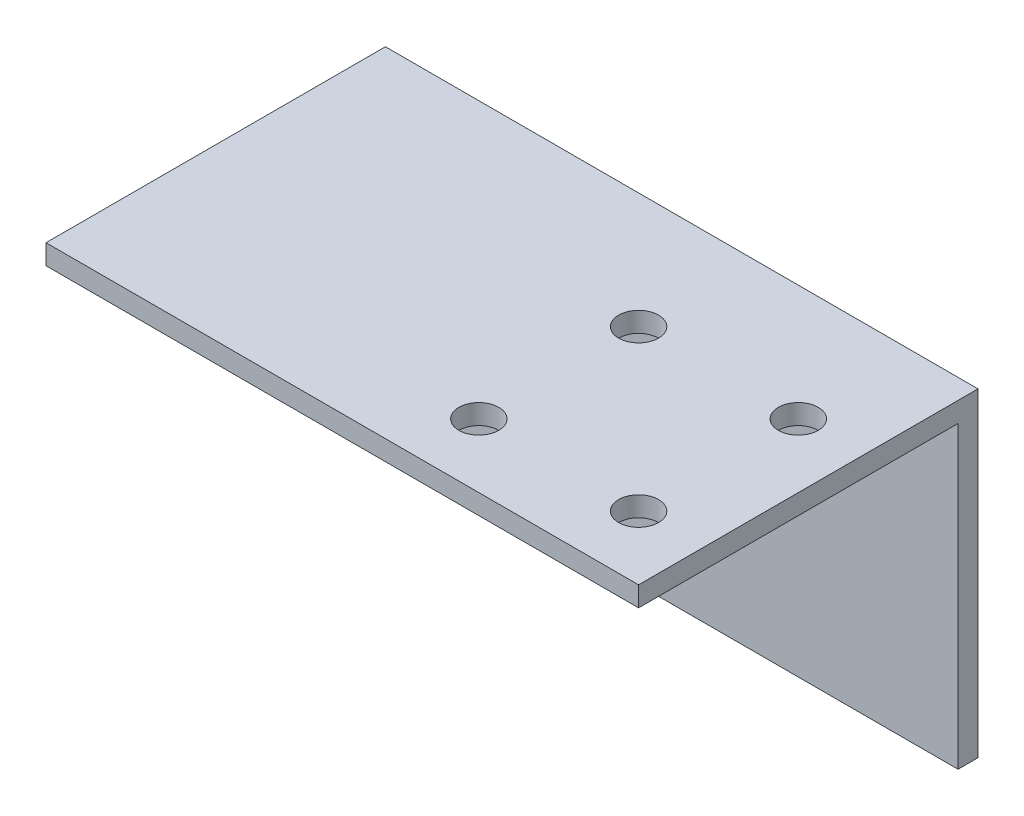
SolidWorks part; units mm, degrees
ref_plane "Front Plane" through (0, 0, 0) normal (0, 0, 1) x (1, 0, 0)
ref_plane "Top Plane" through (0, 0, 0) normal (0, 1, 0) x (1, 0, 0)
ref_plane "Right Plane" through (0, 0, 0) normal (1, 0, 0) x (0, 0, -1)
sketch "Sketch1" plane through (0, 0, 0) normal (0, 0, 1) x (1, 0, 0)
  line L0 (22.86, 50.8) -> (22.86, 0) construction
  line L1 (0, 0) -> (94.234, 0)
  line L2 (0, 0) -> (0, 50.8)
  line L3 (0, 50.8) -> (94.234, 50.8)
  line L4 (94.234, 0) -> (94.234, 50.8)
  line L6 (22.86, 18.4) -> (54.8613, 73.8279) construction
  line L7 (22.86, 18.4) -> (60.1516, -46.1909) construction
  circle A0 centre (22.86, 25.4) radius 4
  circle A1 centre (38.36, 40.9) radius 2
  circle A2 centre (38.36, 9.9) radius 2
  circle A3 centre (7.36, 40.9) radius 2
  circle A4 centre (7.36, 9.9) radius 2
  dimension "D3" = 8
  dimension "D4" = 25.4
  dimension "D7" = 15.5
  dimension "D10" = 15.5
  dimension "D12" = 15.5
  dimension "D15" = 15.5
  dimension "D8" = 4
  dimension "D5" = 4
  dimension "D11" = 4
  dimension "D13" = 4
  dimension "D1" = 94.234
  dimension "D2" = 50.8
  dimension "D6" = 15.5
  dimension "D9" = 22.86
  dimension "D14" = 15.5
extrude "Boss-Extrude1" add sketch "Sketch1" along normal blind 3.175
sketch "Sketch2" plane through (0, 0, 3.175) normal (0, 0, 1) x (1, 0, 0)
  line L0 (94.234, 0) -> (94.234, 50.8) construction
  line L1 (0, 50.8) -> (94.234, 50.8)
  line L2 (0, 50.8) -> (0, 47.625)
  line L3 (0, 47.625) -> (94.234, 47.625)
  line L4 (94.234, 50.8) -> (94.234, 47.625)
  dimension "D1" = 3.175
extrude "Boss-Extrude2" add sketch "Sketch2" along normal blind 50.8
sketch "Sketch3" plane through (0, 47.625, 0) normal (0, -1, 0) x (1, 0, 0)
  line L0 (84.074, 50.165) -> (84.074, -0.635) construction
  line L1 (0, 53.975) -> (94.234, 53.975) construction
  line L4 (94.234, 53.975) -> (94.234, 0) construction
  circle A0 centre (84.074, 43.815) radius 3.175
  circle A1 centre (84.074, 18.415) radius 3.175
  circle A2 centre (58.674, 43.815) radius 3.175
  circle A3 centre (58.674, 18.415) radius 3.175
  dimension "D1" = 6.35
  dimension "D5" = 6.35
  dimension "D6" = 6.35
  dimension "D2" = 25.4
  dimension "D3" = 10.16
  dimension "D4" = 10.16
  dimension "D7" = 25.4
  dimension "D8" = 25.4
  dimension "D9" = 25.4
extrude "Cut-Extrude1" cut sketch "Sketch3" against normal through all
